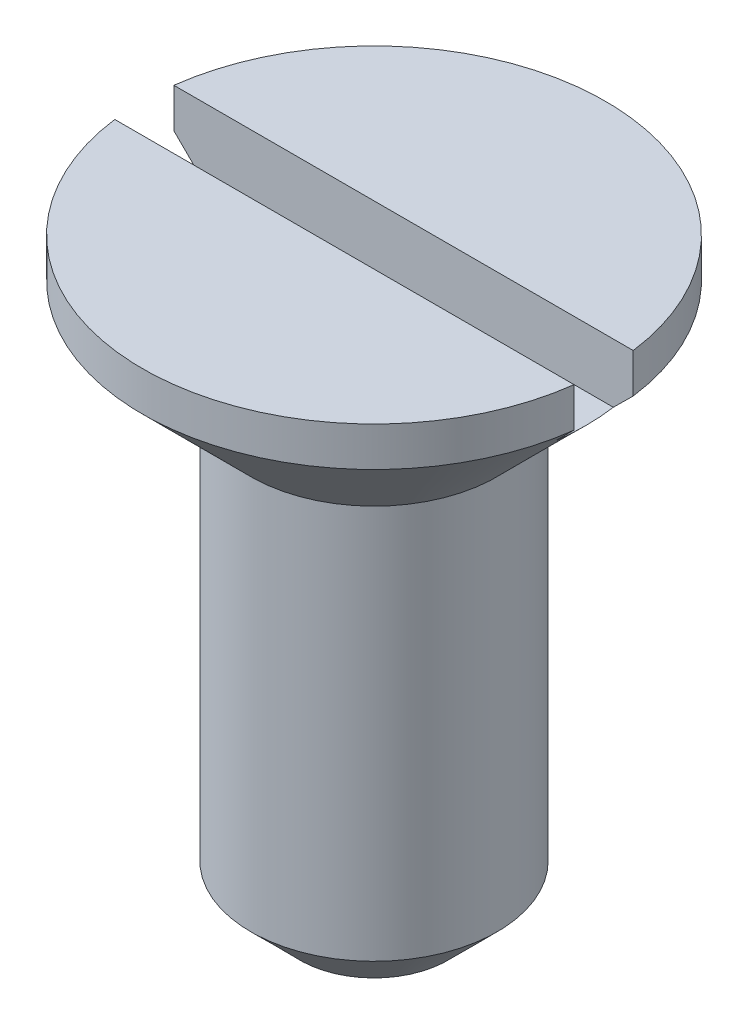
SolidWorks part; units mm, degrees
ref_plane "Спереди" through (0, 0, 0) normal (0, 0, 1) x (1, 0, 0)
ref_plane "Сверху" through (0, 0, 0) normal (0, 1, 0) x (1, 0, 0)
ref_plane "Справа" through (0, 0, 0) normal (1, 0, 0) x (0, 0, -1)
sketch "Эскиз1" plane through (0, 0, 0) normal (0, 0, 1) x (1, 0, 0)
  line L0 (0, 125.7632) -> (0, 0) construction
  line L2 (0, 92.035) -> (0, 86.035)
  line L3 (0, 92.035) -> (2.35, 92.035)
  line L4 (1.25, 90.535) -> (1.25, 86.035)
  line L5 (1.25, 90.535) -> (2.35, 91.635)
  line L6 (1.25, 86.035) -> (0, 86.035)
  line L7 (2.35, 92.035) -> (2.35, 91.635)
  dimension "D1" = 2.35
  dimension "D2" = 6
  dimension "D3" = 1.5
  dimension "D4" = 45
  dimension "D5" = 1.25
revolve "Повернуть1" add sketch "Эскиз1" angle 360 about L0
ref_axis "Ось4" through (0, 2.1934, 0) along (0, -1, 0)
sketch "Эскиз13" plane through (0, 92.035, 0) normal (0, 1, 0) x (-1, 0, 0)
  line L1 (2.35, -0.3) -> (-2.35, -0.3)
  line L2 (2.35, -0.3) -> (2.35, 0.3)
  line L3 (2.35, 0.3) -> (-2.35, 0.3)
  line L4 (-2.35, -0.3) -> (-2.35, 0.3)
  dimension "D1" = 2.35
  dimension "D2" = 4.7
  dimension "D3" = 0.3
  dimension "D4" = 0.6
extrude "Вырез-Вытянуть9" cut sketch "Эскиз13" against normal blind 0.6
chamfer "Фаска1" distance 0.5 angle 45 1 edges at (-1.25, 86.035, 0)
